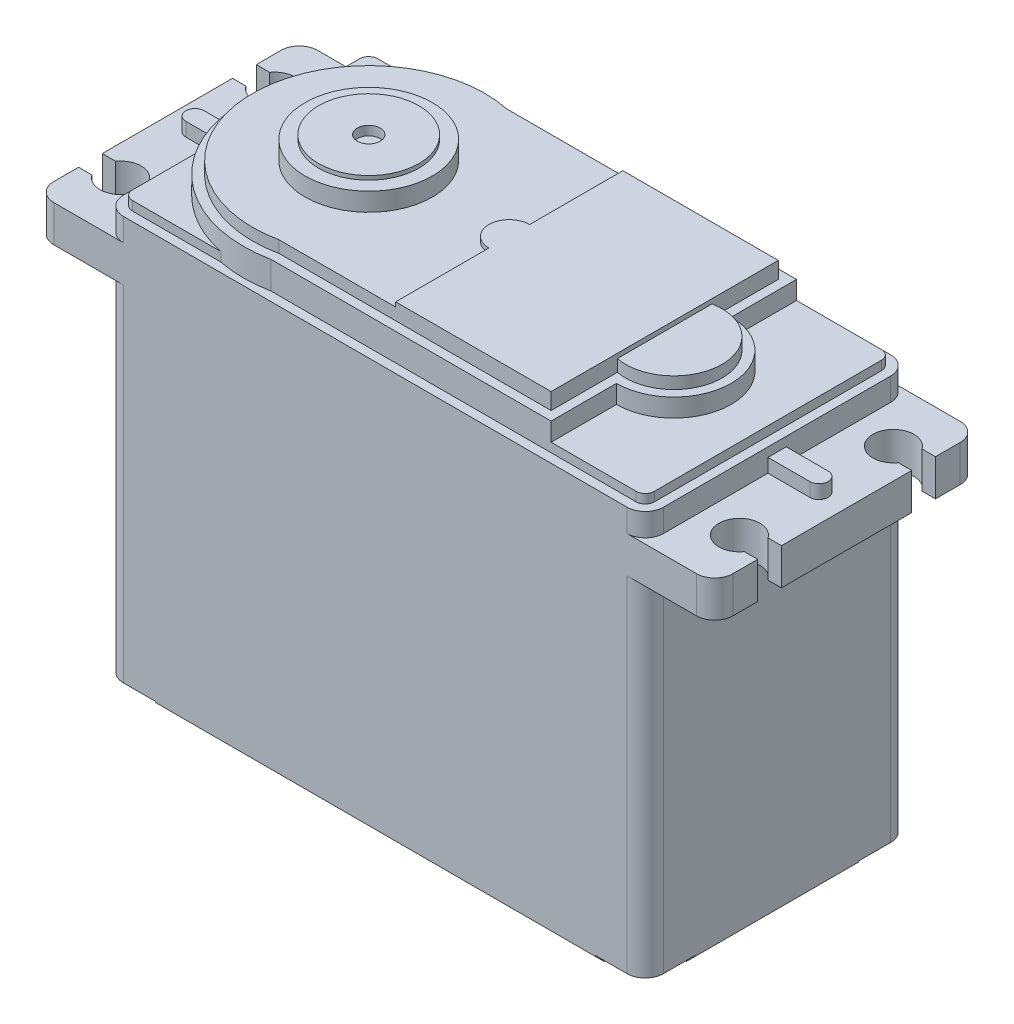
SolidWorks part; units mm, degrees
ref_plane "Alzado" through (0, 0, 0) normal (0, 0, 1) x (1, 0, 0)
ref_plane "Planta" through (0, 0, 0) normal (0, 1, 0) x (1, 0, 0)
ref_plane "Vista lateral" through (0, 0, 0) normal (1, 0, 0) x (0, 0, -1)
sketch "Croquis1" plane through (0, 0, 0) normal (0, 1, 0) x (1, 0, 0)
  line L1 (-29.55, -14.425) -> (29.55, -14.425)
  line L2 (-29.55, -14.425) -> (-29.55, 14.425)
  line L3 (-29.55, 14.425) -> (29.55, 14.425)
  line L4 (29.55, -14.425) -> (29.55, 14.425)
  line L5 (-29.55, -14.425) -> (29.55, 14.425) construction
  line L6 (-29.55, 14.425) -> (29.55, -14.425) construction
  point P0 (0, 0)
  dimension "D1" = 59.1
  dimension "D2" = 28.85
extrude "Saliente-Extruir1" add sketch "Croquis1" along normal mid plane 45.3
sketch "Croquis2" plane through (0, -22.65, 0) normal (0, -1, 0) x (1, 0, 0)
  line L0 (0, 0) -> (0, -50000) construction
  line L1 (29.55, 14.425) -> (24.05, 14.425)
  line L2 (29.55, 14.425) -> (29.55, 8.925)
  line L3 (29.55, 8.925) -> (26.05, 8.925)
  line L4 (24.05, 14.425) -> (24.05, 10.925)
  line L5 (0, 0) -> (50000, 0) construction
  line L6 (-29.55, 14.425) -> (-29.55, 8.925)
  line L7 (-29.55, 14.425) -> (-24.05, 14.425)
  line L8 (-24.05, 14.425) -> (-24.05, 10.925)
  line L9 (-29.55, 8.925) -> (-26.05, 8.925)
  line L10 (0, 0) -> (-50000, 0) construction
  line L11 (24.05, -14.425) -> (24.05, -10.925)
  line L12 (29.55, -8.925) -> (26.05, -8.925)
  line L13 (29.55, -14.425) -> (29.55, -8.925)
  line L14 (29.55, -14.425) -> (24.05, -14.425)
  line L15 (-24.05, -14.425) -> (-24.05, -10.925)
  line L16 (-29.55, -14.425) -> (-24.05, -14.425)
  line L17 (-29.55, -14.425) -> (-29.55, -8.925)
  line L18 (-29.55, -8.925) -> (-26.05, -8.925)
  arc A0 (26.05, -8.925) -> (24.05, -10.925) centre (26.05, -10.925) ccw
  arc A1 (-24.05, -10.925) -> (-26.05, -8.925) centre (-26.05, -10.925) ccw
  arc A2 (-26.05, 8.925) -> (-24.05, 10.925) centre (-26.05, 10.925) ccw
  arc A3 (26.05, 8.925) -> (24.05, 10.925) centre (26.05, 10.925) cw
  point P26 (24.05, -8.925)
  point P29 (-24.05, -8.925)
  point P32 (-24.05, 8.925)
  point P35 (24.05, 8.925)
  dimension "D3" = 2
  dimension "D1" = 5.5
  dimension "D2" = 5.5
extrude "Cortar-Extruir1" cut sketch "Croquis2" against normal blind 1.1
chamfer "Chaflán1" distance 1 angle 45 4 edges at (-29.55, -22.65, 0) (0, -22.65, -14.425) (29.55, -22.65, 0) (0, -22.65, 14.425)
fillet "Redondeo1" radius 2 4 edges at (29.55, 0.55, 14.425) (29.55, 0.55, -14.425) (-29.55, 0.55, -14.425) (-29.55, 0.55, 14.425)
ref_plane "Plano1" through (0, 16.15, 0) normal (0, 1, 0) x (1, 0, 0)
sketch "Croquis3" plane through (0, 16.15, 0) normal (0, 1, 0) x (1, 0, 0)
  line L0 (29.55, -12.425) -> (29.55, 12.425) construction
  line L1 (27.55, 14.425) -> (37.15, 14.425)
  line L2 (-37.15, 0) -> (-50000, 0) construction
  line L3 (27.55, -14.425) -> (37.15, -14.425)
  line L4 (37.15, 14.425) -> (37.15, 9.725)
  line L5 (0, 0) -> (0, -50000) construction
  line L6 (35.6, 7.125) -> (37.15, 7.125)
  line L7 (37.15, 7.125) -> (37.15, -7.125)
  line L8 (35.6, 9.725) -> (37.15, 9.725)
  line L9 (0, 0) -> (27.55, 0) construction
  line L10 (35.6, -9.725) -> (37.15, -9.725)
  line L11 (35.6, -7.125) -> (37.15, -7.125)
  line L12 (37.15, -9.725) -> (37.15, -14.425)
  line L13 (37.15, 0) -> (50000, 0) construction
  line L14 (0, 0) -> (-27.55, 0) construction
  line L15 (-37.15, -9.725) -> (-37.15, -14.425)
  line L16 (-35.6, -7.125) -> (-37.15, -7.125)
  line L17 (-35.6, -9.725) -> (-37.15, -9.725)
  line L18 (-35.6, 9.725) -> (-37.15, 9.725)
  line L19 (-37.15, 7.125) -> (-37.15, -7.125)
  line L20 (-35.6, 7.125) -> (-37.15, 7.125)
  line L21 (-37.15, 14.425) -> (-37.15, 9.725)
  line L22 (-27.55, -14.425) -> (-37.15, -14.425)
  line L23 (-27.55, 14.425) -> (-37.15, 14.425)
  line L24 (29.55, 12.425) -> (29.55, -12.425)
  line L25 (-29.55, 12.425) -> (-29.55, -12.425)
  line L26 (35.6, 9.725) -> (35.6, 7.125)
  line L27 (35.6, -7.125) -> (35.6, -9.725)
  line L28 (-35.6, 9.725) -> (-35.6, 7.125)
  line L29 (-35.6, -7.125) -> (-35.6, -9.725)
  arc A4 (-27.55, 14.425) -> (-29.55, 12.425) centre (-27.55, 12.425) ccw
  arc A5 (-27.55, -14.425) -> (-29.55, -12.425) centre (-27.55, -12.425) cw
  arc A6 (27.55, -14.425) -> (29.55, -12.425) centre (27.55, -12.425) ccw
  arc A7 (27.55, 14.425) -> (29.55, 12.425) centre (27.55, 12.425) cw
  point P11 (36.03, 8.425)
  point P23 (36.03, -8.425)
  point P44 (-36.03, -8.425)
  point P45 (-36.03, 8.425)
  dimension "D2" = 7.6
extrude "Saliente-Extruir2" add sketch "Croquis3" along normal blind 4
fillet "Redondeo2" radius 2 4 edges at (-37.15, 18.15, 14.425) (-37.15, 18.15, -14.425) (37.15, 18.15, -14.425) (37.15, 18.15, 14.425)
sketch "Croquis4" plane through (0, 20.15, 0) normal (0, 1, 0) x (1, 0, 0)
  line L0 (0, 0) -> (35.1, 0) construction
  line L1 (29.55, 12.425) -> (29.55, -12.425) construction
  line L2 (34.1322, -1) -> (29.55, -1)
  line L3 (0, 0) -> (0, -50000) construction
  line L4 (34.1322, 1) -> (29.55, 1)
  line L5 (29.55, -1) -> (29.55, 1)
  line L6 (34.668, -0.8443) -> (29.55, 1) construction
  line L7 (34.668, 0.8443) -> (29.55, -1) construction
  line L8 (-34.668, 0.8443) -> (-29.55, -1) construction
  line L9 (-29.55, -1) -> (-29.55, 1)
  line L10 (-34.1322, 1) -> (-29.55, 1)
  line L11 (-34.1322, -1) -> (-29.55, -1)
  arc A0 (34.1322, 1) -> (34.1322, -1) centre (34.1322, 0) cw
  arc A1 (-34.1322, 1) -> (-34.1322, -1) centre (-34.1322, 0) ccw
  point P3 (32.325, 0)
  point P21 (-32.325, 0)
extrude "Saliente-Extruir3" add sketch "Croquis4" along normal blind 1.5
sketch "Croquis5" plane through (0, 22.65, 0) normal (0, 1, 0) x (1, 0, 0)
  line L8 (-27.55, -13.425) -> (27.55, -13.425)
  line L9 (28.55, -12.425) -> (28.55, 12.425)
  line L10 (27.55, 13.425) -> (-27.55, 13.425)
  line L11 (-28.55, 12.425) -> (-28.55, -12.425)
  line L12 (-27.55, -13.425) -> (27.55, -13.425)
  line L13 (28.55, -12.425) -> (28.55, 12.425)
  line L14 (27.55, 13.425) -> (-27.55, 13.425)
  line L15 (-28.55, 12.425) -> (-28.55, -12.425)
  arc A8 (27.55, -13.425) -> (28.55, -12.425) centre (27.55, -12.425) ccw
  arc A9 (28.55, 12.425) -> (27.55, 13.425) centre (27.55, 12.425) ccw
  arc A10 (-27.55, 13.425) -> (-28.55, 12.425) centre (-27.55, 12.425) ccw
  arc A11 (-28.55, -12.425) -> (-27.55, -13.425) centre (-27.55, -12.425) ccw
  arc A12 (27.55, -13.425) -> (28.55, -12.425) centre (27.55, -12.425) ccw
  arc A13 (28.55, 12.425) -> (27.55, 13.425) centre (27.55, 12.425) ccw
  arc A14 (-27.55, 13.425) -> (-28.55, 12.425) centre (-27.55, 12.425) ccw
  arc A15 (-28.55, -12.425) -> (-27.55, -13.425) centre (-27.55, -12.425) ccw
  dimension "D1" = 1
extrude "Saliente-Extruir4" add sketch "Croquis5" along normal blind 1
sketch "Croquis6" plane through (0, 22.65, 0) normal (0, 1, 0) x (1, 0, 0)
  line L0 (-1024.7876, 0) -> (-28.55, 0) construction
  line L1 (27.55, 13.425) -> (-27.55, 13.425) construction
  line L2 (-12.3938, 13.425) -> (18.25, 13.425)
  line L3 (18.25, -6.275) -> (18.25, -13.425)
  line L4 (-12.3938, -13.425) -> (18.25, -13.425)
  line L5 (18.25, 13.425) -> (18.25, 6.275)
  line L6 (-27.55, -13.425) -> (27.55, -13.425) construction
  line L7 (29.55, -12.425) -> (29.55, 12.425) construction
  line L8 (24.525, 0) -> (50000, 0) construction
  arc A0 (18.25, 6.275) -> (18.25, -6.275) centre (18.25, 0) cw
  arc A1 (-12.3938, 13.425) -> (-12.3938, -13.425) centre (-15.125, 0) ccw
  dimension "D1" = 27.4
  dimension "D3" = 6.275
  dimension "D2" = 11.3
extrude "Saliente-Extruir5" add sketch "Croquis6" along normal blind 3
sketch "Croquis7" plane through (0, 25.65, 0) normal (0, 1, 0) x (1, 0, 0)
  line L8 (17.25, 5.1793) -> (17.25, 12.425)
  line L9 (17.25, 12.425) -> (-12.4964, 12.425)
  line L10 (-12.4964, -12.425) -> (17.25, -12.425)
  line L11 (17.25, -12.425) -> (17.25, -5.1793)
  line L12 (17.25, 5.1793) -> (17.25, 12.425)
  line L13 (17.25, 12.425) -> (-12.4964, 12.425)
  line L14 (-12.4964, -12.425) -> (17.25, -12.425)
  line L15 (17.25, -12.425) -> (17.25, -5.1793)
  arc A5 (17.25, -5.1793) -> (17.25, 5.1793) centre (18.25, 0) ccw
  arc A6 (-12.4964, 12.425) -> (-12.4964, -12.425) centre (-15.125, 0) ccw
  arc A7 (17.25, -5.1793) -> (17.25, 5.1793) centre (18.25, 0) ccw
  arc A8 (-12.4964, 12.425) -> (-12.4964, -12.425) centre (-15.125, 0) ccw
  dimension "D1" = 1
extrude "Saliente-Extruir6" add sketch "Croquis7" along normal blind 1.3
sketch "Croquis8" plane through (0, 26.95, 0) normal (0, 1, 0) x (1, 0, 0)
  line L0 (0, 0) -> (50000, 0) construction
  circle A0 centre (-15.125, 0) radius 6.96
  dimension "D1" = 13.92
extrude "Saliente-Extruir7" add sketch "Croquis8" along normal blind 2
sketch "Croquis9" plane through (0, 28.95, 0) normal (0, 1, 0) x (1, 0, 0)
  circle A0 centre (-15.125, 0) radius 5.485
  dimension "D1" = 10.97
extrude "Saliente-Extruir8" add sketch "Croquis9" along normal blind 0.44
sketch "Croquis10" plane through (0, 29.39, 0) normal (0, 1, 0) x (1, 0, 0)
  circle A0 centre (-15.125, 0) radius 1.25
  dimension "D1" = 2.5
extrude "Cortar-Extruir2" cut sketch "Croquis10" against normal blind 1
hole_wizard "Taladro de margen para M1.61" positions "Croquis12" profile "Croquis11" hole size "M1.6" standard "As"
sketch "Croquis12" plane through (0, -21.55, 0) normal (0, -1, 0) x (-1, 0, 0)
  line L0 (-29.55, 12.425) -> (-29.55, 8.925) construction
  line L1 (-24.05, 14.425) -> (-27.55, 14.425) construction
  point P0 (-27.05, 11.925)
  dimension "D1" = 2.5
  dimension "D2" = 2.5
sketch "Croquis11" plane through (27.05, -21.55, -11.925) normal (1, 0, 0) x (0, 0, -1)
  line L0 (0, 0) -> (0, 5.5408)
  line L1 (0, 5.5408) -> (0.9, 5)
  line L2 (0.9, 5) -> (0.9, 0)
  line L5 (0.9, 0) -> (0, 0)
  line L10 (0, 5.5408) -> (-0.9, 5) construction
  line L11 (0, -6.35) -> (0, 107.95) construction
  dimension "Diámetro de taladro" = 1.8
  dimension "Profundidad de taladro" = 5
  dimension "Ángulo de perforador" = 118
mirror "Simetría1" about plane through (0, 0, 0) normal (0, 0, 1) of "Taladro de margen para M1.61"
mirror "Simetría2" about plane through (0, 0, 0) normal (1, 0, 0) of "Simetría1"
ref_axis "Eje1" through (35.6, 20.15, -8.425) along (-1, 0, 0)
hole_wizard "Taladro de margen para #81" positions "Croquis14" profile "Croquis13" hole size "#8" standard "Ansi Inch" end condition up to next
sketch "Croquis14" plane through (0, 20.15, 0) normal (0, 1, 0) x (1, 0, 0)
  line L0 (37.15, 9.725) -> (37.15, 12.425) construction
  line L1 (35.6, 8.425) -> (-35.6, 8.425) construction
  line L2 (-37.15, 12.425) -> (-37.15, 9.725) construction
  line L3 (-37.15, 7.125) -> (-37.15, -7.125) construction
  point P0 (33.85, 8.425)
  point P7 (33.85, -8.425)
  point P9 (-33.85, 8.425)
  point P11 (-33.85, -8.425)
  dimension "D1" = 3.3
  dimension "D2" = 0
  dimension "D3" = 3.3
  dimension "D4" = 3.3
sketch "Croquis13" plane through (33.85, 20.15, -8.425) normal (1, 0, 0) x (0, 0, 1)
  line L0 (0, 0) -> (0, 4)
  line L1 (0, 4) -> (2.2479, 4)
  line L2 (2.2479, 4) -> (2.2479, 0)
  line L5 (2.2479, 0) -> (0, 0)
  line L11 (0, -6.35) -> (0, 107.95) construction
  dimension "Diámetro de taladro hasta el siguiente" = 4.4958
  dimension "Profundidad de taladro hasta el siguiente" = 4
sketch "Croquis15" plane through (0, 26.95, 0) normal (0, 1, 0) x (1, 0, 0)
  line L0 (-12.4964, -12.425) -> (17.25, -12.425) construction
  line L1 (17.25, 12.425) -> (0.25, 12.425)
  line L2 (17.25, 12.425) -> (17.25, -12.425)
  line L3 (17.25, -12.425) -> (0.25, -12.425)
  line L4 (0.25, 12.425) -> (0.25, 2.23)
  line L5 (0.25, -2.23) -> (0.25, -12.425)
  arc A0 (0.25, 2.23) -> (0.25, -2.23) centre (0.25, 0) ccw
  dimension "D2" = 4.46
  dimension "D1" = 17
extrude "Saliente-Extruir9" add sketch "Croquis15" along normal blind 0.5
sketch "Croquis17" plane through (-29.55, 0, 0) normal (-1, 0, 0) x (0, 0, 1)
  line L0 (0, 0) -> (0, -50000) construction
  line L2 (8.925, -22.65) -> (-8.925, -22.65) construction
  line L3 (-3.62, -14.39) -> (3.62, -14.39)
  line L4 (-3.62, -14.39) -> (-3.62, -18.8)
  line L5 (-3.62, -18.8) -> (3.62, -18.8)
  line L6 (3.62, -14.39) -> (3.62, -18.8)
  line L7 (-3.62, -14.39) -> (3.62, -18.8) construction
  line L8 (-3.62, -18.8) -> (3.62, -14.39) construction
  point P2 (0, -16.595)
  dimension "D1" = 3.85
  dimension "D2" = 7.24
  dimension "D3" = 4.41
ref_plane "Plano4" through (-35.55, 0, 0) normal (-1, 0, 0) x (0, 0, 1)
sketch "Croquis18" plane through (-35.55, 0, 0) normal (-1, 0, 0) x (0, 0, 1)
  line L8 (3.12, -14.89) -> (-3.12, -14.89)
  line L9 (3.12, -18.3) -> (3.12, -14.89)
  line L10 (-3.12, -18.3) -> (3.12, -18.3)
  line L11 (-3.12, -14.89) -> (-3.12, -18.3)
  line L12 (3.12, -14.89) -> (-3.12, -14.89)
  line L13 (3.12, -18.3) -> (3.12, -14.89)
  line L14 (-3.12, -18.3) -> (3.12, -18.3)
  line L15 (-3.12, -14.89) -> (-3.12, -18.3)
  point P0 (0, -16.595)
  dimension "D1" = 0.5
loft "Recubrir1" add profiles "Croquis17", "Croquis18" connector at (-29.55, -14.39, -3.62) connector at (-35.55, -14.89, -3.12)
